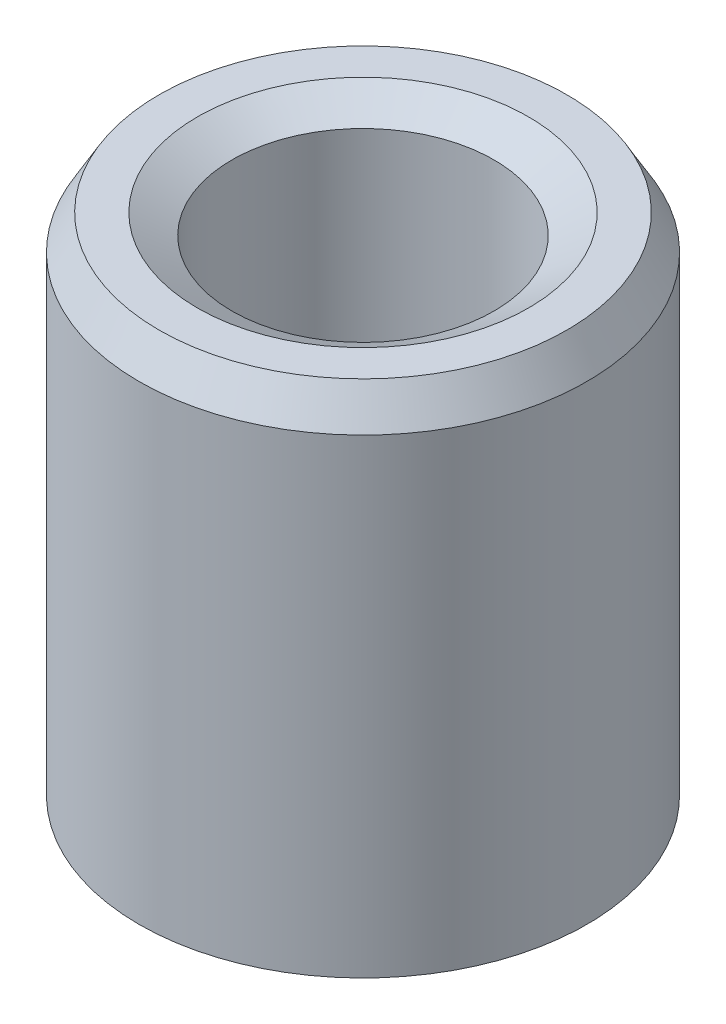
SolidWorks part; units mm, degrees
ref_plane "Front Plane" through (0, 0, 0) normal (0, 0, 1) x (1, 0, 0)
ref_plane "Top Plane" through (0, 0, 0) normal (0, 1, 0) x (1, 0, 0)
ref_plane "Right Plane" through (0, 0, 0) normal (1, 0, 0) x (0, 0, -1)
sketch "Sketch1" plane through (0, 0, 0) normal (0, 1, 0) x (1, 0, 0)
  circle A0 centre (0, 0) radius 15
  dimension "SLEEVE_OD" = 30
extrude "Boss-Extrude1" add sketch "Sketch1" along normal blind 35.159
sketch "Sketch2" plane through (0, 0, 0) normal (0, 1, 0) x (1, 0, 0)
  circle A0 centre (0, 0) radius 8.7792
  dimension "BORE_D" = 17.5583
extrude "Cut-Extrude1" cut sketch "Sketch2" along normal through all
chamfer "Chamfer1" distance 2.3167 angle 30 4 edges at (0, 35.159, 8.7792) (0, 0, 8.7792) (0, 0, 15) (0, 35.159, 15) first distance on face at (0, 35.159, 8.7792) first distance on face at (0, 0, 8.7792) first distance on face at (0, 35.159, 15)
